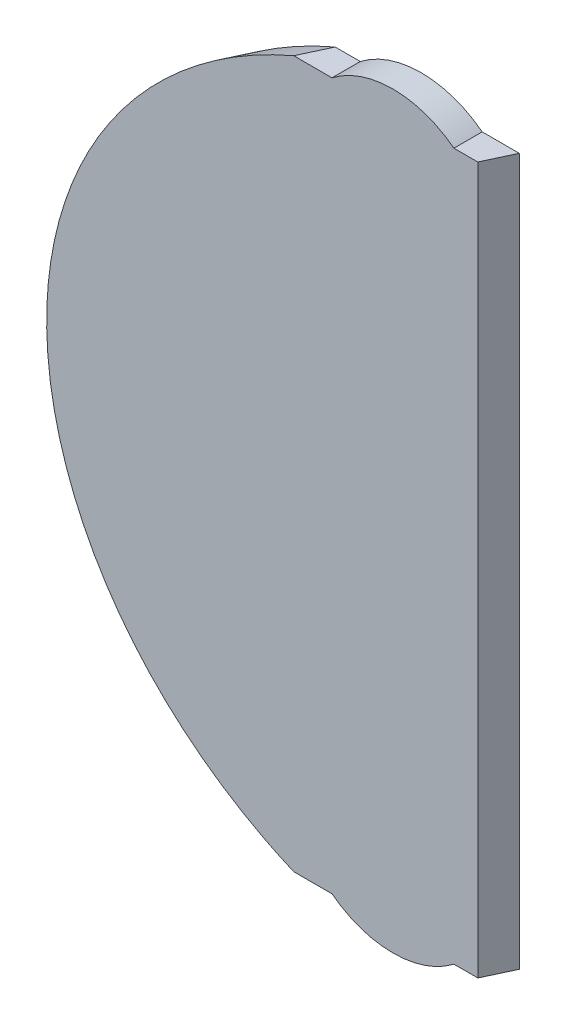
SolidWorks part; units mm, degrees
ref_plane "Front Plane" through (0, 0, 0) normal (0, 0, 1) x (1, 0, 0)
ref_plane "Top Plane" through (0, 0, 0) normal (0, 1, 0) x (1, 0, 0)
ref_plane "Right Plane" through (0, 0, 0) normal (1, 0, 0) x (0, 0, -1)
sketch "Sketch1" plane through (0, 0, 0) normal (0, 0, 1) x (1, 0, 0)
  line L0 (-58.622, 0) -> (58.622, 0) construction
  line L1 (0, 55.0692) -> (0, -55.0692) construction
  line L2 (-2.794, 14.6488) -> (-2.794, -15.4775)
  line L3 (0, 10.795) -> (-13.9598, 10.795)
  line L4 (0, 10.795) -> (0, -10.795)
  line L5 (0, -10.795) -> (-13.9598, -10.795)
  line L6 (-13.9598, 10.795) -> (-13.9598, -10.795)
  line L7 (-2.794, -11.43) -> (-2.794, -8.382)
  line L8 (-10.6662, 11.43) -> (0, 11.43)
  line L9 (-10.6662, 11.43) -> (-10.6662, -11.43)
  line L10 (-10.6662, -11.43) -> (0, -11.43)
  line L11 (0, 11.43) -> (0, -11.43)
  circle A0 centre (0, 0) radius 13.172
  circle A1 centre (-2.794, -8.382) radius 3.048
  ellipse E0 centre (0, 0) end of major axis (-13.172, 0) minor radius 11.938
  dimension "D1" = 21.59
  dimension "D2" = 2.794
  dimension "D3" = 22.86
sketch "Sketch2" plane through (0, 0, 0) normal (0, 0, 1) x (1, 0, 0)
  line L0 (0, 0) -> (-11.938, 0) construction
  line L3 (0, 10.795) -> (-13.9598, 10.795) construction
  line L4 (0, -10.795) -> (-5.6243, -10.795)
  line L5 (0, -10.795) -> (0, 10.795)
  line L6 (-5.6243, 10.795) -> (0, 10.795)
  line L7 (0, -10.795) -> (-13.9598, -10.795) construction
  ellipse E0 centre (0, 0) end of major axis (-13.172, 0) minor radius 11.938 construction
  ellipse E1 centre (0, 0) end of major axis (-13.172, 0) minor radius 11.938 (-5.6243, 10.795) -> (-5.6243, -10.795) ccw
ref_plane "Plane1" through (0, 10.795, 0) normal (0, 1, 0) x (-1, 0, 0)
ref_plane "Plane3" through (0, 0, 0) normal (-0.4226, 0, 0.9063) x (0.9063, 0, 0.4226)
sketch "Sketch6" plane through (0, 0, 0) normal (-0.4226, 0, 0.9063) x (0.9063, 0, 0.4226)
  circle A0 centre (0, 0) radius 11.938
sketch "Sketch3" plane through (0, 10.795, 0) normal (0, 1, 0) x (-1, 0, 0)
  line L0 (0, 0) -> (0.3465, 0.743)
extrude "Extrude1" add sketch "Sketch2" along direction (-0.4226, 0, 0.9063) on the side of the normal mid plane 0.9529
sketch "Sketch4" plane through (0, 0, 0) normal (0, 0, 1) x (1, 0, 0)
  line L0 (0, -10.795) -> (-13.9598, -10.795) construction
  line L1 (-4.6562, -10.795) -> (-0.9318, -10.795)
  line L2 (-58.622, 0) -> (58.622, 0) construction
  line L3 (-4.6562, 10.795) -> (-0.9318, 10.795)
  arc A0 (-4.6562, -10.795) -> (-0.9318, -10.795) centre (-2.794, -8.382) ccw
  circle A1 centre (-2.794, -8.382) radius 3.048 construction
  arc A2 (-4.6562, 10.795) -> (-0.9318, 10.795) centre (-2.794, 8.382) cw
extrude "Extrude2" add sketch "Sketch4" along normal up to surface (0.4318 mm away) up to face at (-4.9004, 0, 0.4318)
ref_plane "Plane2" through (0, 0, 0.4318) normal (0, 0, 1) x (1, 0, 0)
sketch "Sketch5" plane through (0, 0, 0.4318) normal (0, 0, 1) x (1, 0, 0)
  line L0 (-2.794, 11.43) -> (-2.794, -11.43) construction
  line L1 (-2.794, 14.6488) -> (-2.794, -15.4775) construction
  line L2 (-10.6662, 11.43) -> (0, 11.43) construction
extrude "Extrude3" add sketch "Sketch4<2>" against normal up to surface (0.4318 mm away) up to face at (-4.4977, 0, -0.4318)
sketch "Sketch4<2>" plane through (0, 0, 0) normal (0, 0, 1) x (1, 0, 0) same geometry as "Sketch4"
ref_point "Point1"
